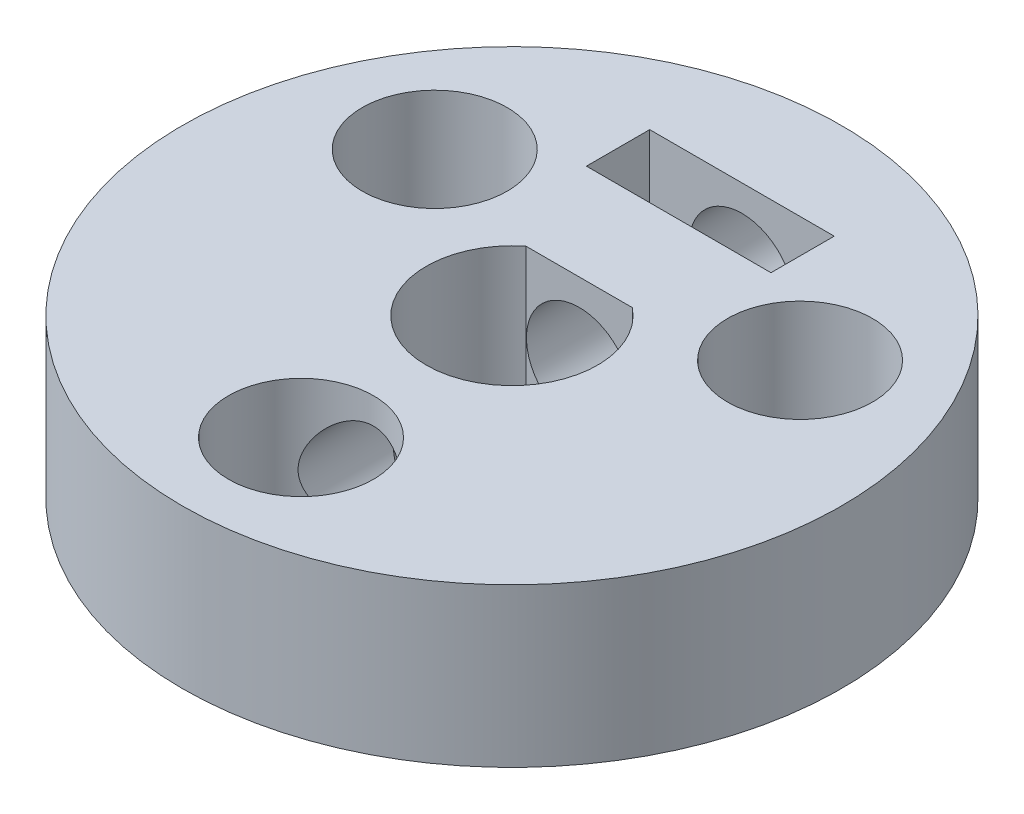
SolidWorks part; units mm, degrees
ref_plane "Front Plane" through (0, 0, 0) normal (0, 0, 1) x (1, 0, 0)
ref_plane "Top Plane" through (0, 0, 0) normal (0, 1, 0) x (1, 0, 0)
ref_plane "Right Plane" through (0, 0, 0) normal (1, 0, 0) x (0, 0, -1)
sketch "Sketch1" plane through (0, 0, 0) normal (0, 1, 0) x (1, 0, 0)
  circle A0 centre (0, 0) radius 12.5
  dimension "D1" = 25
extrude "Boss-Extrude1" add sketch "Sketch1" along normal blind 6
sketch "Sketch2" plane through (0, 6, 0) normal (0, 1, 0) x (1, 0, 0)
  line L0 (-2.0149, 2.55) -> (2.0149, 2.55) construction
  line L1 (0, -3.25) -> (0, 0) construction
  line L2 (-2.0149, 2.55) -> (2.0149, 2.55)
  circle A0 centre (0, 0) radius 3.25
  dimension "D1" = 6.5
  dimension "D2" = 5.8
extrude "Cut-Extrude1" cut sketch "Sketch2" against normal up to next contours L2 A0 region at (0, 6, 0.1745)
sketch "Sketch3" plane through (0, 6, 0) normal (0, 1, 0) x (1, 0, 0)
  line L0 (0, 0) -> (0, -12.5) construction
  circle A0 centre (0, 0) radius 12.5 construction
  circle A1 centre (0, -8) radius 2.75
  circle A2 centre (-6.9282, 4) radius 2.75
  circle A3 centre (6.9282, 4) radius 2.75
  point P15 (0, 0)
  dimension "D1" = 5.5
  dimension "D2" = 8
  dimension "D4" = 6.9282
  dimension "D5" = 4
  dimension "D3" = 3
extrude "Cut-Extrude2" cut sketch "Sketch3" against normal up to next
sketch "Sketch4" plane through (0, 0, -2.55) normal (0, 0, 1) x (1, 0, 0)
  line L0 (0, 0) -> (0, 6) construction
  line L1 (2.0149, 0) -> (-2.0149, 0) construction
  line L2 (-2.0149, 6) -> (2.0149, 6) construction
  circle A0 centre (0, 3) radius 2
  dimension "D1" = 4
extrude "Cut-Extrude3" cut sketch "Sketch4" against normal up to next and the other way up to next
sketch "Sketch5" plane through (0, 6, 0) normal (0, 1, 0) x (1, 0, 0)
  line L0 (0, 2.55) -> (0, 12.5) construction
  line L1 (-2.0149, 2.55) -> (2.0149, 2.55) construction
  line L3 (-3.5, 6.325) -> (3.5, 6.325)
  line L4 (-3.5, 6.325) -> (-3.5, 8.725)
  line L5 (-3.5, 8.725) -> (3.5, 8.725)
  line L6 (3.5, 6.325) -> (3.5, 8.725)
  line L7 (-3.5, 6.325) -> (3.5, 8.725) construction
  line L8 (-3.5, 8.725) -> (3.5, 6.325) construction
  circle A0 centre (0, 0) radius 12.5 construction
  point P7 (0, 7.525)
  dimension "D1" = 7
  dimension "D2" = 2.4
extrude "Cut-Extrude4" cut sketch "Sketch5" against normal up to next
